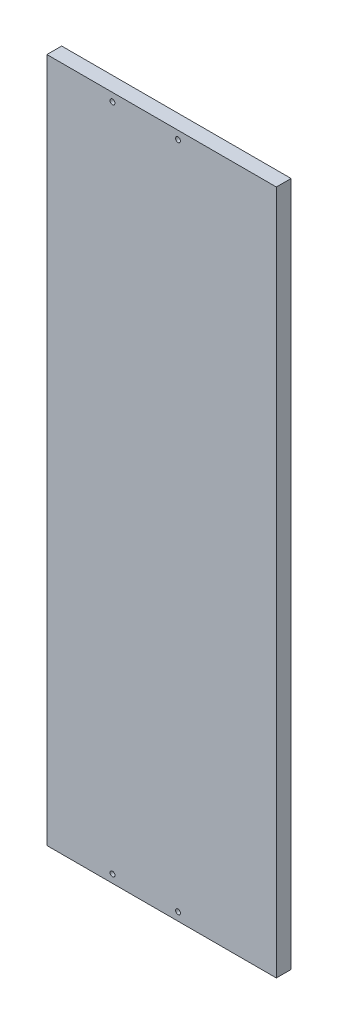
SolidWorks part; units mm, degrees
material "Береза"
ref_plane "Спереди" through (0, 0, 0) normal (0, 0, 1) x (1, 0, 0)
ref_plane "Сверху" through (0, 0, 0) normal (0, 1, 0) x (1, 0, 0)
ref_plane "Справа" through (0, 0, 0) normal (1, 0, 0) x (0, 0, -1)
ref_plane "Плоскость4" through (0, 0, 9) normal (0, 0, 1) x (1, 0, 0)
sketch "Эскиз1" plane through (0, 0, 9) normal (0, 0, 1) x (1, 0, 0)
  line L0 (140, 418) -> (0, 418)
  line L1 (0, 418) -> (0, 0)
  line L2 (0, 0) -> (140, 0)
  line L3 (140, 0) -> (140, 418)
  line L4 (0, 209) -> (140, 209) construction
  circle A0 centre (80, 413) radius 1.5
  circle A1 centre (40, 413) radius 1.5
  circle A2 centre (40, 5) radius 1.5
  circle A3 centre (80, 5) radius 1.5
extrude "Бобышка-Вытянуть1" add sketch "Эскиз1" against normal blind 9
